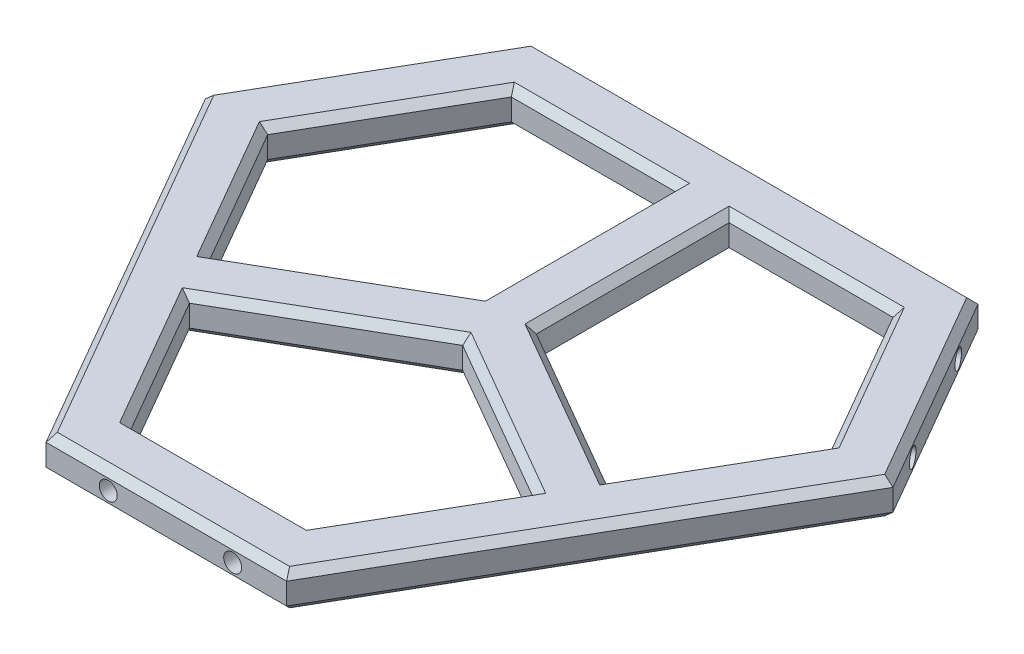
SolidWorks part; units mm, degrees
material "ABS"
ref_plane "Front Plane" through (0, 0, 0) normal (0, 0, 1) x (1, 0, 0)
ref_plane "Top Plane" through (0, 0, 0) normal (0, 1, 0) x (1, 0, 0)
ref_plane "Right Plane" through (0, 0, 0) normal (1, 0, 0) x (0, 0, -1)
sketch "ServoAxisPositions" plane through (0, 0, 0) normal (0, 1, 0) x (1, 0, 0)
  line L0 (-155.8846, -90) -> (155.8846, -90) construction
  line L1 (155.8846, -90) -> (0, 180) construction
  line L2 (0, 180) -> (-155.8846, -90) construction
  line L3 (-103.923, 60) -> (103.923, 60) construction
  line L4 (103.923, 60) -> (0, -120) construction
  line L5 (0, -120) -> (-103.923, 60) construction
  circle A0 centre (0, 0) radius 90 construction
  circle A1 centre (0, 0) radius 60 construction
  point P10 (-69.282, 60)
  point P11 (69.282, 60)
  point P12 (-17.3205, -90)
  point P13 (86.6025, 30)
  point P14 (17.3205, -90)
  point P15 (-86.6025, 30)
  dimension "D1" = 120
  dimension "D2" = 180
  dimension "D3" = 60
  dimension "D4" = 60
  dimension "D5" = 60
  dimension "D6" = 60
sketch "Sketch1" plane through (0, 0, 0) normal (0, 1, 0) x (1, 0, 0)
  line L6 (61.782, 72.9904) -> (-61.782, 72.9904) construction
  line L7 (-95.2628, 15) -> (-34.641, -90) construction
  line L8 (32.3205, -90) -> (94.1025, 17.0096) construction
  line L12 (-103.923, 60) -> (103.923, 60) construction
  line L13 (103.923, 60) -> (0, -120) construction
  line L14 (0, -120) -> (-103.923, 60) construction
  line L15 (155.8846, -90) -> (0, 180) construction
  line L16 (0, 180) -> (-155.8846, -90) construction
  line L17 (-155.8846, -90) -> (155.8846, -90) construction
  line L18 (-61.782, 72.9904) -> (-95.2628, 15)
  line L19 (-95.2628, 15) -> (-34.641, -90)
  line L20 (-34.641, -90) -> (32.3205, -90)
  line L21 (32.3205, -90) -> (94.1025, 17.0096)
  line L22 (94.1025, 17.0096) -> (61.782, 72.9904)
  line L23 (61.782, 72.9904) -> (-61.782, 72.9904)
  dimension "D1" = 15
  dimension "D2" = 15
  dimension "D3" = 15
extrude "Boss-Extrude1" add sketch "Sketch1" along normal blind 5 and the other way blind 5
hole_wizard "M3x6x5 Insert Holes1" positions "Sketch2" profile "Sketch3" hole size "Ø5.0" standard "ANSI Metric"
sketch "Sketch2" plane through (0, 0, 90) normal (0, 0, 1) x (1, 0, 0)
  point P0 (-17.3205, 0)
  point P3 (17.3205, 0)
sketch "Sketch3" plane through (-17.3205, 0, 90) normal (1, 0, 0) x (0, -1, 0)
  line L0 (0, 0) -> (0, 6.5)
  line L1 (0, 6.5) -> (2.5, 6.5)
  line L2 (2.5, 6.5) -> (2.5, 0)
  line L5 (2.5, 0) -> (0, 0)
  line L10 (0, 6.5) -> (-2.5, 6.5) construction
  line L11 (0, -6.35) -> (0, 107.95) construction
  dimension "Hole Dia." = 5
  dimension "Hole Depth" = 6.5
  dimension "Drill Angle" = 180
hole_wizard "M3x6x5 Insert Holes2" positions "Sketch4" profile "Sketch5" hole size "Ø5.0" standard "ANSI Metric"
sketch "Sketch4" plane through (77.9423, 0, -45) normal (0.866, 0, -0.5) x (-0.5, 0, -0.866)
  point P0 (-17.3205, 0)
  point P3 (17.3205, 0)
sketch "Sketch5" plane through (86.6025, 0, -30) normal (0, 1, 0) x (-0.5, 0, -0.866)
  line L0 (0, 0) -> (0, 6.5)
  line L1 (0, 6.5) -> (2.5, 6.5)
  line L2 (2.5, 6.5) -> (2.5, 0)
  line L5 (2.5, 0) -> (0, 0)
  line L10 (0, 6.5) -> (-2.5, 6.5) construction
  line L11 (0, -6.35) -> (0, 107.95) construction
  dimension "Hole Dia." = 5
  dimension "Hole Depth" = 6.5
  dimension "Drill Angle" = 180
hole_wizard "M3x6x5 Insert Holes3" positions "Sketch6" profile "Sketch7" hole size "Ø5.0" standard "ANSI Metric"
sketch "Sketch6" plane through (-77.9423, 0, -45) normal (-0.866, 0, -0.5) x (-0.5, 0, 0.866)
  point P0 (-17.3205, 0)
  point P3 (17.3205, 0)
sketch "Sketch7" plane through (-69.282, 0, -60) normal (0, 1, 0) x (-0.5, 0, 0.866)
  line L0 (0, 0) -> (0, 6.5)
  line L1 (0, 6.5) -> (2.5, 6.5)
  line L2 (2.5, 6.5) -> (2.5, 0)
  line L5 (2.5, 0) -> (0, 0)
  line L10 (0, 6.5) -> (-2.5, 6.5) construction
  line L11 (0, -6.35) -> (0, 107.95) construction
  dimension "Hole Dia." = 5
  dimension "Hole Depth" = 6.5
  dimension "Drill Angle" = 180
sketch "Sketch10" plane through (0, 5, 0) normal (0, 1, 0) x (1, 0, 0)
  line L6 (0, 0) -> (0, 57.9904) construction
  line L7 (0, 0) -> (-51.9615, -30) construction
  line L8 (0, 0) -> (50.2211, -28.9952) construction
  line L9 (7.5, 0) -> (7.5, 57.9904) construction
  line L10 (-3.75, -6.4952) -> (46.4711, -35.4904) construction
  line L11 (-3.75, 6.4952) -> (-55.7115, -23.5048) construction
  line L12 (53.1218, 57.9904) -> (-53.1218, 57.9904)
  line L13 (-53.1218, 57.9904) -> (-77.9423, 15)
  line L14 (-77.9423, 15) -> (-25.9808, -75)
  line L15 (-25.9808, -75) -> (23.6603, -75)
  line L16 (23.6603, -75) -> (76.782, 17.0096)
  line L17 (76.782, 17.0096) -> (53.1218, 57.9904)
  line L18 (53.1218, 57.9904) -> (-53.1218, 57.9904) construction
  line L19 (-53.1218, 57.9904) -> (-77.9423, 15) construction
  line L20 (-77.9423, 15) -> (-25.9808, -75) construction
  line L21 (-25.9808, -75) -> (23.6603, -75) construction
  line L22 (23.6603, -75) -> (76.782, 17.0096) construction
  line L23 (76.782, 17.0096) -> (53.1218, 57.9904) construction
  line L24 (-7.5, 0) -> (-7.5, 57.9904) construction
  line L25 (3.75, 6.4952) -> (53.9711, -22.5) construction
  line L26 (3.75, -6.4952) -> (-48.2115, -36.4952) construction
  line L27 (-7.5, 57.9904) -> (-53.1218, 57.9904)
  line L28 (-53.1218, 57.9904) -> (-77.9423, 15)
  line L29 (-77.9423, 15) -> (-55.7115, -23.5048)
  line L30 (-55.7115, -23.5048) -> (-7.5, 4.3301)
  line L31 (-7.5, 4.3301) -> (-7.5, 57.9904)
  line L32 (7.5, 57.9904) -> (53.1218, 57.9904)
  line L33 (53.1218, 57.9904) -> (76.782, 17.0096)
  line L34 (76.782, 17.0096) -> (53.9711, -22.5)
  line L35 (53.9711, -22.5) -> (7.5, 4.3301)
  line L36 (7.5, 4.3301) -> (7.5, 57.9904)
  line L37 (46.4711, -35.4904) -> (23.6603, -75)
  line L38 (23.6603, -75) -> (-25.9808, -75)
  line L39 (-25.9808, -75) -> (-48.2115, -36.4952)
  line L40 (-48.2115, -36.4952) -> (0, -8.6603)
  line L41 (0, -8.6603) -> (46.4711, -35.4904)
  dimension "D1" = 15
  dimension "D2" = 7.5
  dimension "D3" = 7.5
extrude "Cut-Extrude3" cut sketch "Sketch10" against normal through all
chamfer "Chamfer3" distance 2 angle 45 42 edges at (-78.5224, -5, -43.9952) (-64.9519, -5, 37.5) (-1.1603, -5, 90) (63.2115, -5, 36.4952) (77.9423, -5, -45) (0, -5, -72.9904) (64.9519, -5, -37.5) (65.3766, -5, 2.7452) (30.7356, -5, 9.0849) (7.5, -5, -31.1603) (30.3109, -5, -57.9904) (-7.5, -5, -31.1603) (-31.6058, -5, 9.5873) (-66.8269, -5, 4.2524) (-65.532, -5, -36.4952) (-30.3109, -5, -57.9904) (-1.1603, -5, 75) (-37.0961, -5, 55.7476) (-24.1058, -5, 22.5777) (23.2356, -5, 22.0753) (35.0657, -5, 55.2452) (77.9423, 5, -45) (63.2115, 5, 36.4952) (-1.1603, 5, 90) (-64.9519, 5, 37.5) (-78.5224, 5, -43.9952) (0, 5, -72.9904) (30.7356, 5, 9.0849) (65.3766, 5, 2.7452) (64.9519, 5, -37.5) (30.3109, 5, -57.9904) (7.5, 5, -31.1603) (-66.8269, 5, 4.2524) (-31.6058, 5, 9.5873) (-7.5, 5, -31.1603) (-30.3109, 5, -57.9904) (-65.532, 5, -36.4952) (-24.1058, 5, 22.5777) (-37.0961, 5, 55.7476) (-1.1603, 5, 75) (35.0657, 5, 55.2452) (23.2356, 5, 22.0753)
equation "\"Platform_Ext_radius\" = 90mm"
equation "\"Platform_Int_radius\"= 60mm"
equation "\"D1@ServoAxisPositions\"=\"Platform_Int_radius\"*2"
equation "\"D2@ServoAxisPositions\"=\"Platform_Ext_radius\"*2"
